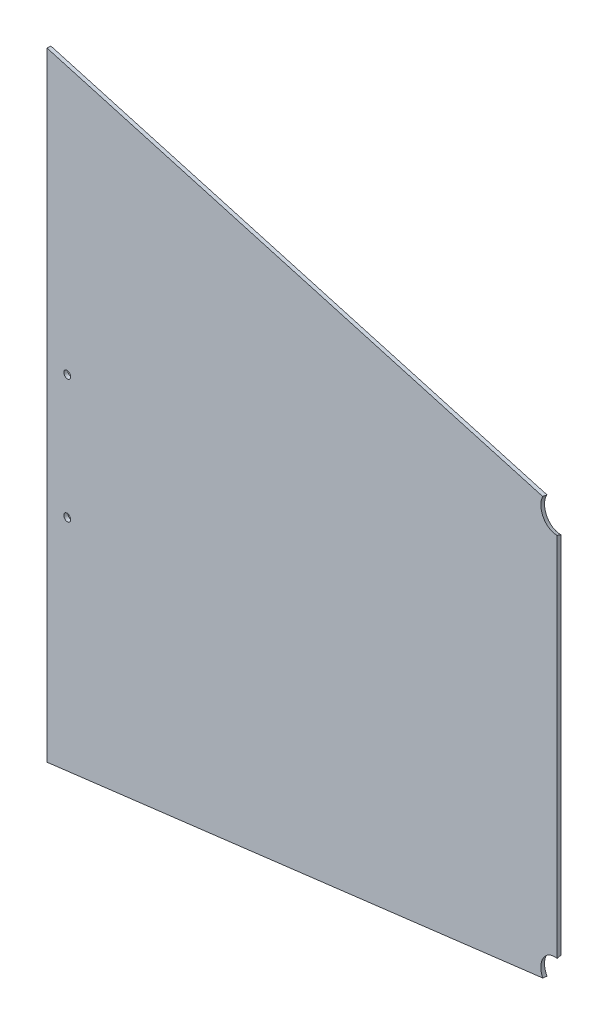
SolidWorks part; units mm, degrees
material "6061-T6 (SS)"
ref_plane "X-Y Datum" through (0, 0, 0) normal (0, 0, 1) x (1, 0, 0)
ref_plane "X-Z Datum" through (0, 0, 0) normal (0, 1, 0) x (1, 0, 0)
ref_plane "Y-Z Datum" through (0, 0, 0) normal (1, 0, 0) x (0, 0, -1)
ref_plane "Plane1" through (1.0099, 0, -13.5995) normal (0.0741, 0, -0.9973) x (-0.9973, 0, -0.0741)
ref_plane "Plane2" through (1.9503, 0, -26.2646) normal (0.0741, 0, -0.9973) x (-0.9973, 0, -0.0741)
sketch "Sketch1" plane through (1.9503, 0, -26.2646) normal (0.0741, 0, -0.9973) x (-0.9973, 0, -0.0741)
  line L0 (-183.6444, -298.45) -> (-183.6444, 298.45) construction
  line L1 (-183.6444, -298.45) -> (-826.7602, -177.8) construction
  line L2 (-826.7602, -177.8) -> (-826.7602, 177.8) construction
  line L3 (-826.7602, 177.8) -> (-183.6444, 298.45) construction
  line L4 (-183.6444, -298.45) -> (-183.6444, 298.45)
  line L5 (-183.6444, -298.45) -> (-826.7602, -177.8)
  line L6 (-826.7602, -177.8) -> (-826.7602, 177.8)
  line L7 (-826.7602, 177.8) -> (-183.6444, 298.45)
extrude "Boss-Extrude1" add sketch "Sketch1" along normal blind 3.175
ref_plane "Plane3" through (825.5, 212.9428, 150.983) normal (0, 0.3219, 0.9468) x (1, 0, 0)
sketch "Sketch2" plane through (825.5, 212.9428, 150.983) normal (0, 0.3219, 0.9468) x (1, 0, 0)
  circle A0 centre (0, 0) radius 14.2875
  dimension "D1" = 28.575
extrude "Cut-Extrude1" cut sketch "Sketch2" against normal through all contours A0
mirror "Mirror1" about plane through (0, 0, 0) normal (0, 1, 0) of "Cut-Extrude1"
sketch "Sketch3" plane through (1.9503, 0, -26.2646) normal (-0.0741, 0, 0.9973) x (0.9973, 0, 0.0741)
  line L0 (348.7444, 267.4769) -> (348.7444, -267.4769)
  line L1 (813.2196, -180.3402) -> (183.6444, -298.45) construction
  line L2 (183.6444, -298.45) -> (183.6444, 298.45) construction
  line L3 (183.6444, 298.45) -> (813.2196, 180.3402) construction
  point P5 (348.7444, 0)
  line M2 (183.6444, -298.45) -> (813.2196, -180.3402)
  line M6 (813.2196, 180.3402) -> (183.6444, 298.45)
  line M7 (183.6444, 298.45) -> (183.6444, -298.45)
  dimension "D1" = 165.1
extrude "Cut-Extrude2" cut sketch "Sketch3" against normal through all contours L0 M6 M7 M2 region at (265.912, 0, -6.6635)
sketch "Sketch4" plane through (2.1855, 0, -29.4309) normal (0.0741, 0, -0.9973) x (-0.9973, 0, -0.0741)
  line L0 (-336.0444, 33) -> (-367.7944, 33) construction
  line L1 (-336.0444, -74) -> (-367.7944, -74) construction
  line L2 (-348.7444, 267.4769) -> (-348.7444, -267.4769) construction
  line L3 (-348.7444, 267.4769) -> (-348.7444, -267.4769)
  circle A0 centre (-367.7944, 33) radius 3.175
  circle A1 centre (-367.7944, -74) radius 3.175
  point P0 (-336.0444, 33)
  point P1 (-336.0444, -74)
  point P2 (-336.0444, -74)
  dimension "D1" = 6.35
  dimension "D2" = 19.05
extrude "Cut-Extrude3" cut sketch "Sketch4" against normal through all contours A0 | A1 region at (368.97, 33, -2.1945) region at (368.97, -74, -2.1945)
